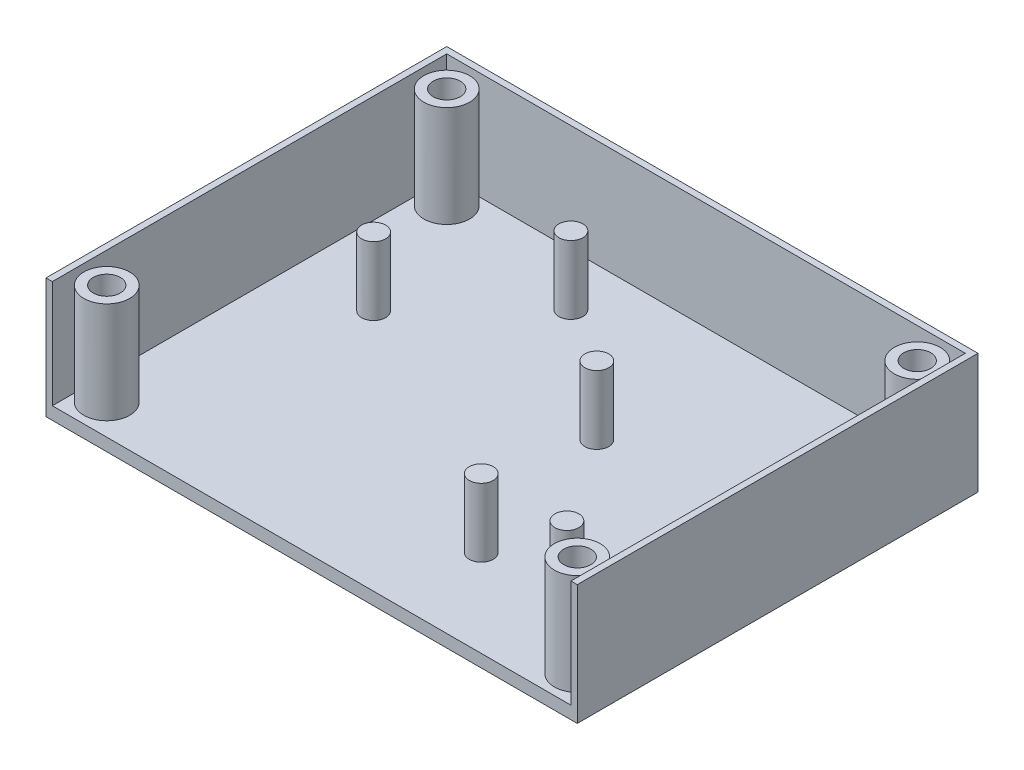
SolidWorks part; units mm, degrees
ref_plane "Front Plane" through (0, 0, 0) normal (0, 0, 1) x (1, 0, 0)
ref_plane "Top Plane" through (0, 0, 0) normal (0, 1, 0) x (1, 0, 0)
ref_plane "Right Plane" through (0, 0, 0) normal (1, 0, 0) x (0, 0, -1)
sketch "Sketch1" plane through (0, 0, 0) normal (0, 1, 0) x (1, 0, 0)
  line L0 (-66.8583, -50.2762) -> (-65.2708, -50.2762)
  line L1 (-65.2708, -50.2762) -> (64.8554, -50.2762)
  line L2 (-66.8583, -50.2762) -> (-66.8583, 50.2663)
  line L3 (-66.8583, 50.2663) -> (66.4429, 50.2663)
  line L4 (66.4429, -50.2762) -> (66.4429, 50.2663)
  line L5 (66.4429, -50.2762) -> (64.8554, -50.2762)
  line L6 (-50.3864, 41.1329) -> (-50.3864, 5.0649)
  line L7 (-50.3483, 41.1463) -> (49.9329, 41.1463)
  line L8 (-65.2708, -50.2762) -> (-65.2708, 48.6788)
  line L9 (-65.2708, 48.6788) -> (64.8554, 48.6788)
  line L10 (64.8554, -50.2762) -> (64.8554, 48.6788)
  line L11 (-50.3483, 41.1463) -> (-50.3483, -40.1162)
  line L12 (-50.3483, -40.1162) -> (49.9329, -40.1162)
  line L13 (49.9329, 41.1463) -> (49.9329, -40.1162)
  line L14 (-50.3864, 5.0649) -> (14.3836, 5.0649)
  line L15 (14.3836, 5.0649) -> (14.3836, -33.7971)
  line L16 (14.3836, -33.7971) -> (47.4036, -33.7971)
  line L17 (47.4036, -33.7971) -> (47.4036, 41.1329)
  line L18 (47.4036, 41.1329) -> (-50.3864, 41.1329)
  circle A0 centre (-59.2383, 42.6463) radius 3.4
  circle A1 centre (-59.2383, 42.6463) radius 5.75
  circle A2 centre (58.8229, 42.6463) radius 5.75
  circle A3 centre (58.8229, 42.6463) radius 3.4
  circle A4 centre (-59.2383, -42.6562) radius 5.75
  circle A5 centre (-59.2383, -42.6562) radius 3.4
  circle A6 centre (58.8229, -42.6562) radius 5.75
  circle A7 centre (58.8229, -42.6562) radius 3.4
  circle A8 centre (-21.0872, 35.6529) radius 3
  circle A9 centre (20.4128, -28.3471) radius 3
  circle A10 centre (-45.5872, 10.6529) radius 3
  circle A11 centre (10.4128, 10.6529) radius 3
  circle A12 centre (41.4128, -27.8471) radius 3
  point P0 (0, 0)
  dimension "D5" = 7.62
  dimension "D7" = 7.62
  dimension "D18" = 97.79
  dimension "D20" = 64.77
  dimension "D26" = 24.5
  dimension "D1" = 133.3013
  dimension "D2" = 100.5425
  dimension "D3" = 1.5875
  dimension "D4" = 1.5875
  dimension "D6" = 7.62
  dimension "D8" = 7.62
  dimension "D9" = 7.62
  dimension "D10" = 7.62
  dimension "D11" = 7.62
  dimension "D12" = 7.62
  dimension "D13" = 1.5875
  dimension "D14" = 9.12
  dimension "D15" = 16.51
  dimension "D16" = 16.51
  dimension "D17" = 81.2625
  dimension "D19" = 36.068
  dimension "D21" = 74.93
  dimension "D22" = 5.588
  dimension "D23" = 5.588
  dimension "D24" = 7.366
  dimension "D25" = 56
  dimension "D27" = 25
  dimension "D28" = 10
  dimension "D29" = 21
  dimension "D30" = 39
  dimension "D31" = 0.5
extrude "Boss-Extrude12" add sketch "Sketch1" along normal blind 3.175 contours L0 L1 L5 L4 L3 L2
extrude "Boss-Extrude13" add sketch "Sketch1<23>" along normal blind 30.1625 contours L10 L5 L4 L3 L2 L0 L8 L9 region at (-66.6913, 0, 0.005)
sketch "Sketch1<23>" plane through (0, 0, 0) normal (0, 1, 0) x (1, 0, 0) same geometry as "Sketch1"
extrude "Boss-Extrude15" add sketch "Sketch1<25>" along normal blind 28.575 contours A1 A0 | A2 A3 | A6 A7 | A4 A5 region at (-64.8257, 0, -42.6463) region at (53.2356, 0, -42.6463) region at (-64.8257, 0, 42.6562) region at (53.2356, 0, 42.6562)
sketch "Sketch1<25>" plane through (0, 0, 0) normal (0, 1, 0) x (1, 0, 0) same geometry as "Sketch1"
extrude "Cut-Extrude3" cut sketch "Sketch1<27>" along normal blind 28.575 contours A5 | A5 | A0 | A3 | A7 region at (-59.2383, 0, 42.6562)
sketch "Sketch1<27>" plane through (0, 0, 0) normal (0, 1, 0) x (1, 0, 0) same geometry as "Sketch1"
chamfer "Chamfer2" distance 1.45 angle 45 4 edges at (58.8229, 0, 46.0562) (58.8229, 0, -39.2463) (-59.2383, 0, 46.0562) (-59.2383, 0, -39.2463)
extrude "Boss-Extrude16" add sketch "Sketch1<28>" along normal blind 20.32 contours A12 | A9 | A8 | A10 | A11 region at (20.4128, 0, 28.3471) region at (41.4128, 0, 27.8471)
sketch "Sketch1<28>" plane through (0, 0, 0) normal (0, 1, 0) x (1, 0, 0) same geometry as "Sketch1"
